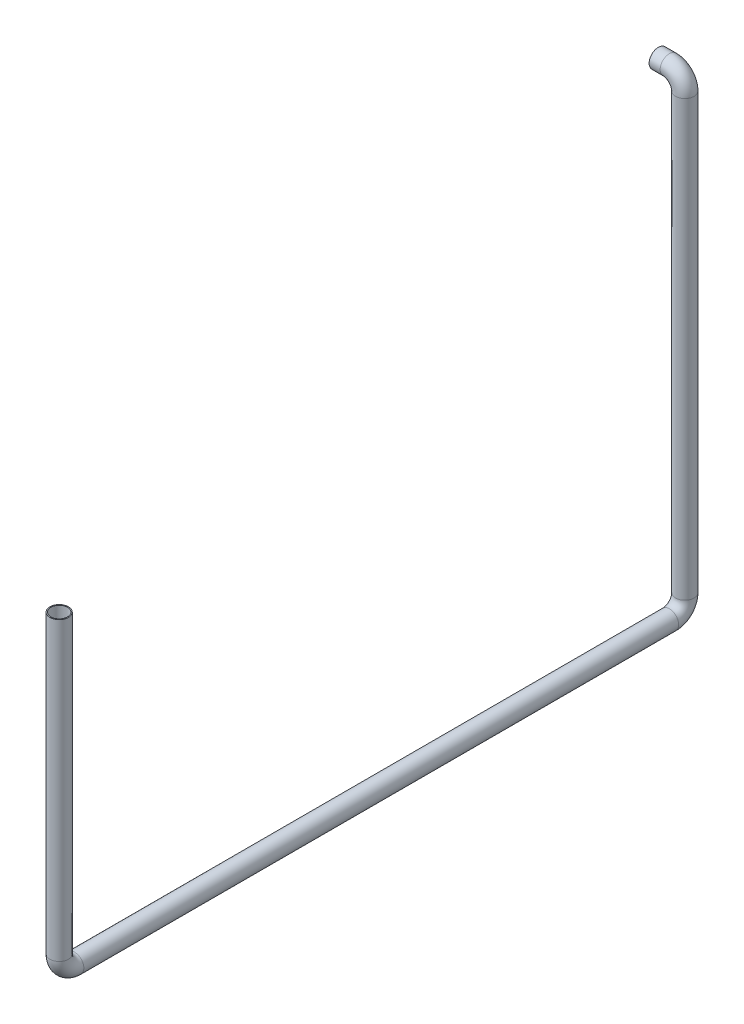
SolidWorks part; units mm, degrees
ref_plane "Plano frontal" through (0, 0, 0) normal (0, 0, 1) x (1, 0, 0)
ref_plane "Plano superior" through (0, 0, 0) normal (0, 1, 0) x (1, 0, 0)
ref_plane "Plano direito" through (0, 0, 0) normal (1, 0, 0) x (0, 0, -1)
sketch3d "3DSketch1"
  line L0 (-29015.6177, -12302.0186, 42898.3002) -> (-29015.6177, -12281.0655, 42898.3002) construction
  line L1 (-29015.6177, -12281.0655, 42898.3002) -> (-29015.6177, -13240.4513, 42898.3002)
  line L2 (-29015.6177, -13290.4513, 42848.3002) -> (-29015.6177, -13290.4513, 40920.7002)
  line L3 (-29015.6177, -13240.4513, 40870.7002) -> (-29015.6177, -11832.5186, 40870.7002)
  line L4 (-29205.8586, -11782.5186, 40870.7002) -> (-29101.3208, -11782.5186, 40870.7002) construction
  line L5 (-29101.3208, -11782.5186, 40870.7002) -> (-29065.6177, -11782.5186, 40870.7002)
  circle A0 centre (-29015.6177, -12302.0186, 42898.3002) radius 15 construction
  circle A1 centre (-29205.8586, -11782.5186, 40870.7002) radius 53.61 construction
  arc A2 (-29065.6177, -11782.5186, 40870.7002) -> (-29015.6177, -11832.5186, 40870.7002) centre (-29065.6177, -11832.5186, 40870.7002) ccw
  arc A3 (-29015.6177, -13240.4513, 40870.7002) -> (-29015.6177, -13290.4513, 40920.7002) centre (-29015.6177, -13240.4513, 40920.7002) ccw
  arc A4 (-29015.6177, -13290.4513, 42848.3002) -> (-29015.6177, -13240.4513, 42898.3002) centre (-29015.6177, -13240.4513, 42848.3002) ccw
  point P4 (-29015.6177, -12317.0186, 42898.3002)
  point P13 (-29152.2486, -11782.5186, 40870.7002)
  point P14 (0, 0, 0)
  point P16 (-29015.6177, -11782.5186, 40870.7002)
  point P17 (-29065.6177, -11832.5186, 40820.7002)
  point P20 (-29015.6177, -13290.4513, 40870.7002)
  point P21 (-29065.6177, -13240.4513, 40920.7002)
  point P24 (-29015.6177, -13290.4513, 42898.3002)
  point P25 (-29065.6177, -13240.4513, 42848.3002)
  dimension "D1" = 50
sweep "Sweep-Thin1" add path "3DSketch1" circular profile diameter 60 parameters "D1"=3, "D3"=60
